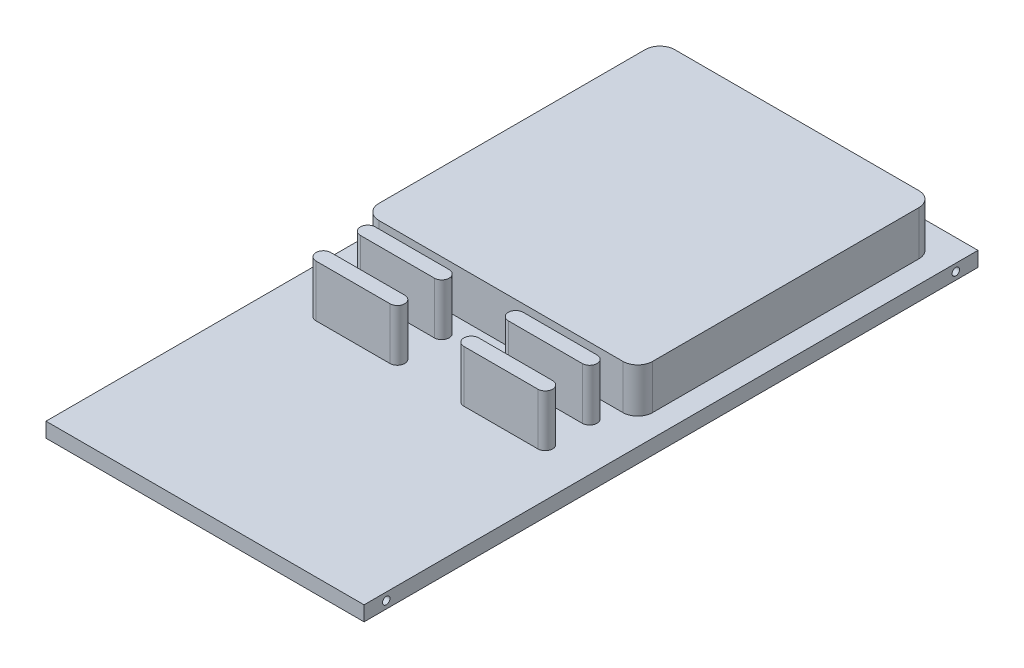
SolidWorks part; units mm, degrees
ref_plane "Front Plane" through (0, 0, 0) normal (0, 0, 1) x (1, 0, 0)
ref_plane "Top Plane" through (0, 0, 0) normal (0, 1, 0) x (1, 0, 0)
ref_plane "Right Plane" through (0, 0, 0) normal (1, 0, 0) x (0, 0, -1)
sketch "Sketch1" plane through (0, 0, 0) normal (0, 1, 0) x (1, 0, 0)
  line L1 (0, 0) -> (54.61, 0)
  line L2 (0, 0) -> (0, 105.41)
  line L3 (0, 105.41) -> (54.61, 105.41)
  line L4 (54.61, 0) -> (54.61, 105.41)
  dimension "D1" = 105.41
  dimension "D2" = 54.61
extrude "Boss-Extrude1" add sketch "Sketch1" along normal blind 2.54
sketch "Sketch2" plane through (0, 2.54, 0) normal (0, 1, 0) x (1, 0, 0)
  line L0 (0, 39.37) -> (54.61, 39.37) construction
  line L1 (0, 105.41) -> (0, 0) construction
  line L2 (54.61, 0) -> (54.61, 105.41) construction
  line L3 (0, 46.99) -> (54.61, 46.99) construction
  line L4 (0, 0) -> (54.61, 0) construction
  line L5 (27.305, 105.41) -> (27.305, 0) construction
  line L6 (54.61, 105.41) -> (0, 105.41) construction
  line L7 (8.255, 39.37) -> (20.955, 39.37) construction
  line L8 (8.255, 40.64) -> (20.955, 40.64)
  line L9 (8.255, 38.1) -> (20.955, 38.1)
  line L10 (46.355, 39.37) -> (33.655, 39.37) construction
  line L11 (46.355, 40.64) -> (33.655, 40.64)
  line L12 (46.355, 38.1) -> (33.655, 38.1)
  line L13 (8.255, 46.99) -> (20.955, 46.99) construction
  line L14 (8.255, 48.26) -> (20.955, 48.26)
  line L15 (8.255, 45.72) -> (20.955, 45.72)
  line L16 (46.355, 46.99) -> (33.655, 46.99) construction
  line L17 (46.355, 48.26) -> (33.655, 48.26)
  line L18 (46.355, 45.72) -> (33.655, 45.72)
  arc A1 (8.255, 40.64) -> (8.255, 38.1) centre (8.255, 39.37) ccw
  arc A2 (20.955, 38.1) -> (20.955, 40.64) centre (20.955, 39.37) ccw
  arc A3 (46.355, 40.64) -> (46.355, 38.1) centre (46.355, 39.37) cw
  arc A4 (33.655, 38.1) -> (33.655, 40.64) centre (33.655, 39.37) cw
  arc A5 (8.255, 48.26) -> (8.255, 45.72) centre (8.255, 46.99) ccw
  arc A6 (20.955, 45.72) -> (20.955, 48.26) centre (20.955, 46.99) ccw
  arc A7 (46.355, 48.26) -> (46.355, 45.72) centre (46.355, 46.99) cw
  arc A8 (33.655, 45.72) -> (33.655, 48.26) centre (33.655, 46.99) cw
  point P18 (14.605, 39.37)
  point P25 (40.005, 39.37)
  point P32 (14.605, 46.99)
  point P39 (40.005, 46.99)
  dimension "D1" = 39.37
  dimension "D3" = 46.99
  dimension "D4" = 14.605
  dimension "D5" = 2.54
  dimension "D6" = 12.7
  dimension "D7" = 14.605
  dimension "D8" = 12.7
  dimension "D9" = 2.54
extrude "Boss-Extrude2" add sketch "Sketch2" along normal blind 8.89
sketch "Sketch3" plane through (0, 0, 0) normal (0, 0, 1) x (1, 0, 0)
  line L0 (0, 0) -> (0, 10.16) construction
  dimension "D1" = 10.16
sketch "Sketch4" plane through (0, 0, 0) normal (-1, 0, 0) x (0, 0, 1)
  line L0 (-105.41, 1.27) -> (0, 1.27) construction
  line L1 (-105.41, 2.54) -> (-105.41, 0) construction
  line L2 (0, 0) -> (0, 10.16) construction
  line L3 (-52.705, 2.54) -> (-52.705, 0) construction
  line L4 (-105.41, 2.54) -> (0, 2.54) construction
  line L5 (-105.41, 0) -> (0, 0) construction
  circle A0 centre (-101.6, 1.27) radius 0.635
  circle A1 centre (-3.81, 1.27) radius 0.635
  dimension "D1" = 1.27
  dimension "D2" = 3.81
extrude "Cut-Extrude1" cut sketch "Sketch4" against normal blind 10.16
ref_plane "Plane1" through (27.305, 0, 0) normal (-1, 0, 0) x (0, 0, 1)
mirror "Mirror1" about plane through (27.305, 0, 0) normal (-1, 0, 0) of "Cut-Extrude1"
sketch "Sketch5" plane through (0, 2.54, 0) normal (0, 1, 0) x (1, 0, 0)
  line L0 (0, 76.2) -> (54.61, 76.2) construction
  line L1 (0, 105.41) -> (0, 0) construction
  line L2 (54.61, 0) -> (54.61, 105.41) construction
  line L3 (54.61, 105.41) -> (0, 105.41) construction
  line L5 (3.81, 50.8) -> (50.8, 50.8)
  line L6 (3.81, 50.8) -> (3.81, 101.6)
  line L7 (3.81, 101.6) -> (50.8, 101.6)
  line L8 (50.8, 50.8) -> (50.8, 101.6)
  line L9 (3.81, 50.8) -> (50.8, 101.6) construction
  line L10 (3.81, 101.6) -> (50.8, 50.8) construction
  point P8 (27.305, 76.2)
  dimension "D2" = 3.81
  dimension "D1" = 29.21
  dimension "D3" = 3.81
extrude "Boss-Extrude3" add sketch "Sketch5" along normal blind 7.62
fillet "Fillet1" radius 2.54 4 edges at (50.8, 6.35, -50.8) (50.8, 6.35, -101.6) (3.81, 6.35, -101.6) (3.81, 6.35, -50.8)
